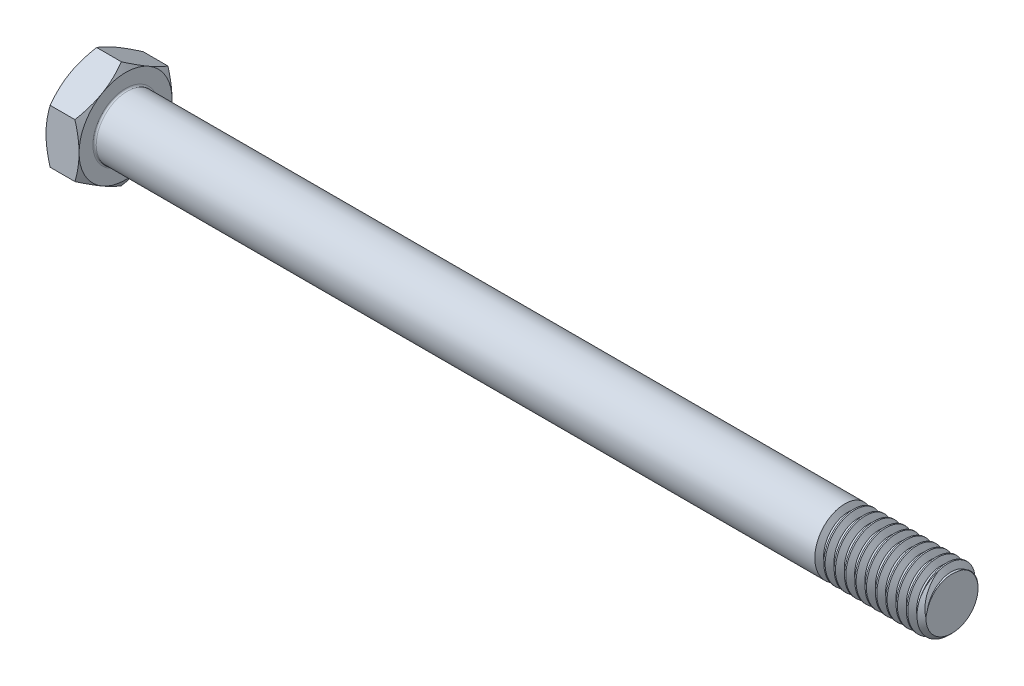
SolidWorks part; units mm, degrees
material "Plain Carbon Steel"
ref_plane "Front Plane" through (0, 0, 0) normal (0, 0, 1) x (1, 0, 0)
ref_plane "Top Plane" through (0, 0, 0) normal (0, 1, 0) x (1, 0, 0)
ref_plane "Right Plane" through (0, 0, 0) normal (1, 0, 0) x (0, 0, -1)
sketch "Sketch1" plane through (0, 0, 0) normal (0, 0, 1) x (1, 0, 0)
  line L0 (0, 0) -> (132.08, 0) construction
  line L1 (132.08, 0) -> (132.08, 4.0005)
  line L3 (131.318, 4.7625) -> (5.334, 4.7625)
  line L4 (5.08, 5.0165) -> (5.08, 7.1437)
  line L5 (5.08, 7.1437) -> (4.4419, 8.2489)
  line L6 (4.4419, 8.2489) -> (0.6381, 8.2489)
  line L7 (0.6381, 8.2489) -> (0, 7.1438)
  line L8 (0, 7.1438) -> (0, 0)
  line L9 (132.08, 4.0005) -> (131.318, 4.7625)
  line L10 (0, 8.2489) -> (-7.1438, 4.1244) construction
  line L11 (-7.1438, 4.1244) -> (-7.1438, -4.1244) construction
  line L12 (-7.1438, -4.1244) -> (0, -8.2489) construction
  line L13 (0, -8.2489) -> (7.1437, -4.1244) construction
  line L14 (7.1437, -4.1244) -> (7.1437, 4.1244) construction
  line L15 (7.1437, 4.1244) -> (0, 8.2489) construction
  line L16 (0, 0) -> (132.08, 0)
  arc A0 (5.334, 4.7625) -> (5.08, 5.0165) centre (5.334, 5.0165) cw
  circle A1 centre (0, 0) radius 7.1438 construction
  point P5 (132.08, 4.7625)
  dimension "D5" = 14.2875
  dimension "D7" = 0.254
  dimension "D1" = 9.525
  dimension "D2" = 127
  dimension "D3" = 30
  dimension "D6" = 5.08
revolve "Revolve1" add sketch "Sketch1" angle 360 about L16
sketch "Sketch2" plane through (0, 0, 0) normal (-1, 0, 0) x (0, 0, 1)
  line L1 (0, 8.2489) -> (-7.1438, 4.1244)
  line L2 (-7.1438, 4.1244) -> (-7.1437, -4.1244)
  line L3 (-7.1437, -4.1244) -> (0, -8.2489)
  line L4 (0, -8.2489) -> (7.1438, -4.1244)
  line L5 (7.1438, -4.1244) -> (7.1437, 4.1244)
  line L6 (7.1437, 4.1244) -> (0, 8.2489)
  circle A0 centre (0, 0) radius 7.1438 construction
  circle A1 centre (0, 0) radius 8.2489 construction
extrude "Cut-Extrude1" cut sketch "Sketch2" against normal through all flip side to cut
thread "Thread1" pitch 1.5875 method cut profile "Thread Profile1" start angle 0, offset 2.54, length 18.415, pitch 1.5875, diameter 9.525
ref_plane "Plane1" through (134.62, 0, 4.7625) normal (0, -1, 0) x (0, 0, 1)
sketch "Thread Profile1" plane through (134.62, 0, 4.7625) normal (0, -1, 0) x (0, 0, 1)
  line L0 (0, 0) -> (0, 1.5875) construction
  line L11 (0, 0) -> (0, 1.3891)
  line L12 (0, 1.3891) -> (-0.8593, 0.893)
  line L13 (-0.8593, 0.893) -> (-0.8593, 0.4961)
  line L15 (-0.8593, 0.4961) -> (0, 0)
  line L17 (-0.8593, 0.6945) -> (0, 0.6945) construction
  point P2 (0, 0)
  dimension "Pitch" = 1.5875
  dimension "Profile_Angle" = 60
  dimension "Profile_Land" = 0.3969
  dimension "Profile_Height" = 0.8593
sketch "Sketch6" plane through (0, -0.0005, 0.0004) normal (0, 0.809, -0.5878) x (1, 0, 0)
  line L4 (115.708, 3.9012) -> (116.2041, 4.7604)
  line L5 (116.2041, 4.7604) -> (114.815, 4.7604)
  line L6 (114.815, 4.7604) -> (115.3111, 3.9012)
  line L7 (115.3111, 3.9012) -> (115.708, 3.9012)
  line L8 (115.708, 3.9012) -> (116.2041, 4.7604)
  line L9 (116.2041, 4.7604) -> (114.815, 4.7604)
  line L10 (114.815, 4.7604) -> (115.3111, 3.9012)
  line L11 (115.3111, 3.9012) -> (115.708, 3.9012)
  dimension "D1" = 0
extrude "Cut-Extrude2" cut sketch "Sketch6" against normal through all
